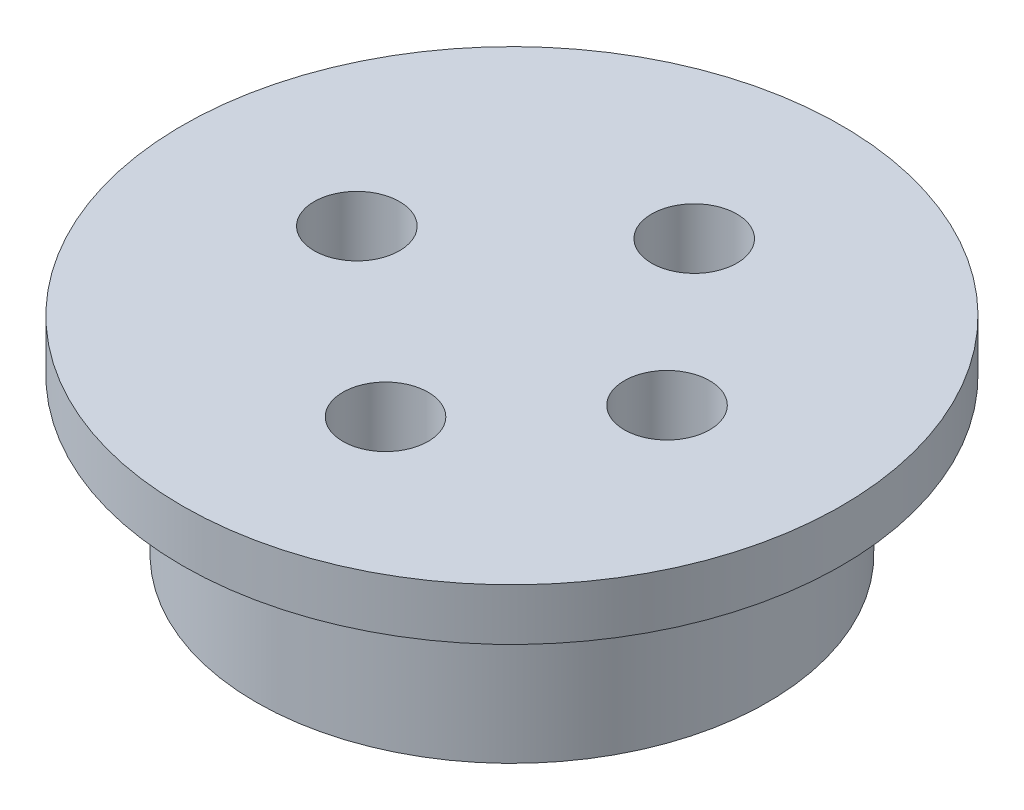
SolidWorks part; units mm, degrees
ref_plane "Front Plane" through (0, 0, 0) normal (0, 0, 1) x (1, 0, 0)
ref_plane "Top Plane" through (0, 0, 0) normal (0, 1, 0) x (1, 0, 0)
ref_plane "Right Plane" through (0, 0, 0) normal (1, 0, 0) x (0, 0, -1)
sketch "Sketch2" plane through (0, 0, 0) normal (0, 1, 0) x (1, 0, 0)
  line L0 (-2.9307, 0.8046) -> (-2.9307, 6.4784) construction
  line L1 (-2.9307, 6.4784) -> (-2.9307, -5.7206) construction
  line L2 (-2.9307, 0.8046) -> (18.0842, 0.8046) construction
  line L3 (-2.9307, 0.8046) -> (-17.2552, 0.8046) construction
  line L4 (-0.9307, 0.8046) -> (-0.9307, 12.9421) construction
  line L5 (-0.9307, 12.9421) -> (-0.9307, -12.4741) construction
  line L6 (1.0693, 0.8046) -> (1.0693, 13.2973) construction
  line L7 (1.0693, 13.2973) -> (1.0693, -12.7898) construction
  line L8 (0.0122, 12.9421) -> (0.0122, -11.6083) construction
  circle A0 centre (-0.9307, 0.8046) radius 9.9
  circle A2 centre (0.0122, 6.9141) radius 1.65
  circle A3 centre (0.0122, 6.9141) radius 3
  circle A4 centre (0.0122, -5.028) radius 1.65
  circle A5 centre (0.0122, -5.028) radius 3
  circle A6 centre (0.0122, 6.9141) radius 2.85 construction
  circle A7 centre (0.0122, -5.028) radius 2.85 construction
  circle A8 centre (-0.9307, 0.8046) radius 12.75
  circle A10 centre (-6.9307, 0.8046) radius 1.65
  circle A11 centre (5.0693, 0.8046) radius 1.65
  dimension "D1" = 19.8
  dimension "D5" = 3.3
  dimension "D6" = 6
  dimension "D7" = 3.3
  dimension "D8" = 6
  dimension "D11" = 25.5
  dimension "D13" = 3.3
  dimension "D14" = 3.3
  dimension "D2" = 2
  dimension "D3" = 2
  dimension "D15" = 6
  dimension "D16" = 6
extrude "Boss-Extrude1" add sketch "Sketch2" against normal blind 8 contours A0
extrude "Boss-Extrude2" add sketch "Sketch2<3>" against normal blind 2 contours A8
sketch "Sketch2<3>" plane through (0, 0, 0) normal (0, 1, 0) x (1, 0, 0) same geometry as "Sketch2"
extrude "Cut-Extrude1" cut sketch "Sketch2<4>" against normal through all contours A10 | A2 | A4 | A11
sketch "Sketch2<4>" plane through (0, 0, 0) normal (0, 1, 0) x (1, 0, 0) same geometry as "Sketch2"
extrude "Cut-Extrude2" cut sketch "Sketch2<5>" along normal blind 3.1 from surface contours A5 | A3 starting at face at (-6.9307, -8, 0.8454)
sketch "Sketch2<5>" plane through (0, 0, 0) normal (0, 1, 0) x (1, 0, 0) same geometry as "Sketch2"
